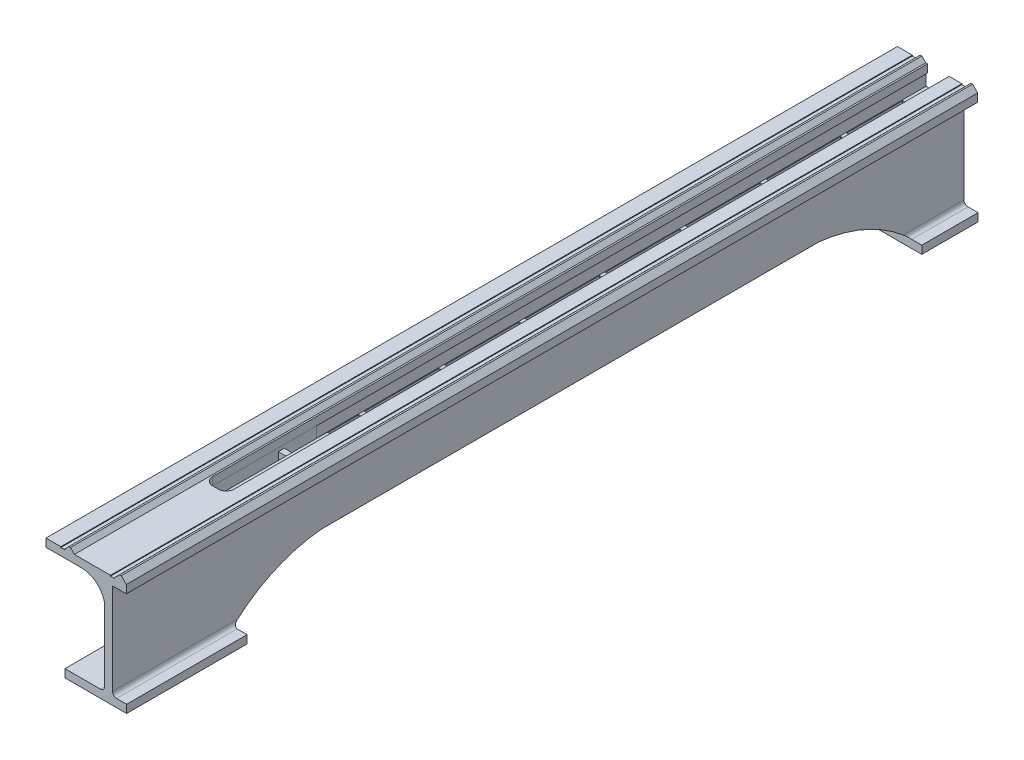
SolidWorks part; units mm, degrees
ref_plane "Front Plane" through (0, 0, 0) normal (0, 0, 1) x (1, 0, 0)
ref_plane "Top Plane" through (0, 0, 0) normal (0, 1, 0) x (1, 0, 0)
ref_plane "Right Plane" through (0, 0, 0) normal (1, 0, 0) x (0, 0, -1)
sketch "Sketch1" plane through (0, 0, 0) normal (0, 0, 1) x (1, 0, 0)
  line L0 (-31.5551, 31.2902) -> (-37.8538, 37.7187)
  line L2 (-131.555, 31.42) -> (-131.555, 21.42)
  line L4 (-31.5551, 31.2902) -> (-31.5551, 21.2902)
  line L5 (-37.8538, 37.7187) -> (-39.8538, 37.7187)
  line L6 (-39.8538, 37.7187) -> (-46.2824, 31.42)
  line L7 (-46.2824, 31.42) -> (-46.2824, 30.42)
  line L8 (-46.2824, 30.42) -> (-51.2824, 30.42)
  line L9 (-51.2824, 30.42) -> (-51.2824, 31.42)
  line L10 (-51.2824, 31.42) -> (-96.2063, 31.42)
  line L14 (-96.2063, 31.42) -> (-101.1053, 36.42)
  line L15 (-101.1053, 36.42) -> (-103.1053, 36.42)
  line L16 (-103.1053, 36.42) -> (-108.055, 31.4703)
  line L17 (-108.055, 31.4703) -> (-108.055, 30.42)
  line L18 (-108.055, 30.42) -> (-113.055, 30.42)
  line L19 (-113.055, 30.42) -> (-113.055, 31.42)
  line L20 (-113.055, 31.42) -> (-131.555, 31.42)
  line L21 (-131.555, 21.42) -> (-87.3496, 21.42)
  line L22 (-31.5551, 21.2902) -> (-48.7011, 21.2902)
  line L23 (-48.7011, 21.2902) -> (-48.7011, -92.58)
  line L24 (-43.7011, -97.58) -> (-31.1954, -97.58)
  line L25 (-31.1954, -97.58) -> (-31.1954, -107.58)
  line L26 (-31.1954, -107.58) -> (-108.01, -107.58)
  line L27 (-108.01, -107.58) -> (-108.01, -97.58)
  line L28 (-108.01, -97.58) -> (-63.7011, -97.58)
  line L29 (-58.7011, -92.58) -> (-58.7011, -1.9527)
  arc A0 (-87.3496, 21.42) -> (-58.7011, -1.9527) centre (-87.3496, -7.8239) cw
  arc A1 (-48.7011, -92.58) -> (-43.7011, -97.58) centre (-43.7011, -92.58) ccw
  arc A2 (-63.7011, -97.58) -> (-58.7011, -92.58) centre (-63.7011, -92.58) ccw
  point P30 (-48.7011, -97.58)
  dimension "D17" = 5
  dimension "D1" = 100
  dimension "D2" = 7
  dimension "D3" = 2
  dimension "D4" = 5
  dimension "D5" = 18.5
  dimension "D6" = 5
  dimension "D7" = 10
  dimension "D8" = 135
  dimension "D9" = 9
  dimension "D10" = 9
  dimension "D11" = 2
  dimension "D12" = 7
  dimension "D13" = 10
  dimension "D14" = 5
  dimension "D15" = 10
  dimension "D16" = 139
  dimension "D18" = 10
  dimension "D19" = 1
extrude "Boss-Extrude1" add sketch "Sketch1" along normal blind 1060
sketch "Sketch2" plane through (0, 20.7647, 0) normal (0, 1, 0) x (1, 0, 0)
  line L0 (-94.1707, -1200) -> (-94.1707, 0) construction
  line L1 (-84.1707, 100) -> (-77.1707, 100)
  line L2 (-94.1707, 90) -> (-94.1707, -890)
  line L3 (-84.1707, -900) -> (-77.1707, -900)
  line L4 (-67.1707, 90) -> (-67.1707, -890)
  line L5 (-67.1707, -1200) -> (-67.1707, 0) construction
  line L6 (-51.2824, 0) -> (-96.2063, 0) construction
  arc A0 (-94.1707, -890) -> (-84.1707, -900) centre (-84.1707, -890) ccw
  arc A1 (-77.1707, -900) -> (-67.1707, -890) centre (-77.1707, -890) ccw
  arc A2 (-77.1707, 100) -> (-67.1707, 90) centre (-77.1707, 90) cw
  arc A3 (-84.1707, 100) -> (-94.1707, 90) centre (-84.1707, 90) ccw
  point P12 (-67.1707, -900)
  point P15 (-67.1707, 100)
  point P18 (-94.1707, 100)
  dimension "D2" = 10
  dimension "D1" = 1000
  dimension "D3" = 100
extrude "Cut-Extrude1" cut sketch "Sketch2" along normal blind 800
sketch "Sketch5" plane through (0, 0, 0) normal (0, 0, -1) x (-1, 0, 0)
  line L1 (105.3464, -97.4955) -> (94.9198, -97.4955)
  line L2 (105.3464, -97.4955) -> (105.3464, 27.7967)
  line L3 (105.3464, 27.7967) -> (94.9198, 27.7967)
  line L4 (94.9198, -97.4955) -> (94.9198, 27.7967)
extrude "Boss-Extrude2" add sketch "Sketch5" against normal blind 950
sketch "Sketch6" plane through (-105.3464, 0, 0) normal (-1, 0, 0) x (0, 0, 1)
  line L0 (0, -97.4955) -> (0, 21.42) construction
  line L1 (0, 16.5847) -> (7.4351, 16.5847)
  line L2 (0, 16.5847) -> (0, -47.4448)
  line L3 (0, -47.4448) -> (7.4351, -47.4448)
  line L4 (7.4351, 16.5847) -> (7.4351, -47.4448)
extrude "Boss-Extrude3" add sketch "Sketch6" against normal blind 50
pattern_linear "LPattern1" count 10 spacing 100 along (0, 0, 1) of "Boss-Extrude3"
sketch "Sketch4" plane through (-31.5551, 0, 0) normal (1, 0, 0) x (0, 0, -1)
  line L0 (-910, -97.58) -> (-910, -107.58)
  line L1 (-1060, -97.58) -> (0, -97.58) construction
  line L2 (-1060, -107.58) -> (0, -107.58) construction
  line L3 (-910, -107.58) -> (-910, -177.9566)
  line L4 (-910, -177.9566) -> (-70, -177.9566)
  line L5 (-70, -177.9566) -> (-70, -97.58)
  line L6 (-800, -47.58) -> (-180.0688, -47.58)
  line L7 (0, -92.58) -> (0, 21.2902) construction
  line L8 (-1060, -92.58) -> (-1060, 21.2902) construction
  arc A1 (-800, -47.58) -> (-910, -97.58) centre (-783.4011, -230.0975) ccw
  arc A2 (-180.0688, -47.58) -> (-70, -97.58) centre (-201.6096, -241.1508) cw
  dimension "D1" = 60
  dimension "D2" = 70
  dimension "D3" = 150
  dimension "D4" = 110
  dimension "D5" = 110.0688
extrude "Cut-Extrude3" cut sketch "Sketch4" against normal blind 100 and the other way blind 10
sketch "Sketch3" plane through (0, 0, 1060) normal (0, 0, 1) x (1, 0, 0)
  line L0 (-51.2824, 31.42) -> (-96.2063, 31.42) construction
  line L1 (-58.7011, 6.42) -> (-95.7995, 6.42)
  line L2 (-58.7011, 6.42) -> (-58.7011, 21.42)
  line L3 (-58.7011, 21.42) -> (-95.7995, 21.42)
  line L4 (-95.7995, 6.42) -> (-95.7995, 21.42)
  line L5 (-58.7011, -1.9527) -> (-58.7011, -47.4448) construction
  dimension "D1" = 15
  dimension "D2" = 10
extrude "Cut-Extrude2" cut sketch "Sketch3" against normal blind 1000 from offset 300 offset against normal yes
sketch "Sketch7" plane through (0, 0, 0) normal (0, 0, -1) x (-1, 0, 0)
  line L0 (58.7011, 6.42) -> (95.7995, 6.42) construction
  line L1 (99.7499, 6.42) -> (57.7636, 6.42)
  line L2 (99.7499, 6.42) -> (99.7499, -7.7909)
  line L3 (99.7499, -7.7909) -> (57.7636, -7.7909)
  line L4 (57.7636, 6.42) -> (57.7636, -7.7909)
extrude "Boss-Extrude4" add sketch "Sketch7" against normal blind 30
sketch "Sketch8" plane through (0, 6.42, 0) normal (0, 1, 0) x (1, 0, 0)
  circle A0 centre (-79.7891, -14.9723) radius 3.8743
extrude "Cut-Extrude4" cut sketch "Sketch8" against normal blind 30
